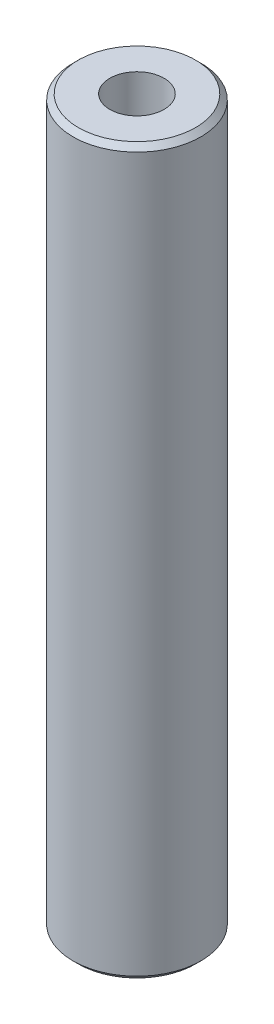
SolidWorks part; units mm, degrees
material "6061-T6 (SS)"
ref_plane "Alzado" through (0, 0, 0) normal (0, 0, 1) x (1, 0, 0)
ref_plane "Planta" through (0, 0, 0) normal (0, 1, 0) x (1, 0, 0)
ref_plane "Vista lateral" through (0, 0, 0) normal (1, 0, 0) x (0, 0, -1)
sketch "Croquis2" plane through (0, 0, 0) normal (0, 1, 0) x (1, 0, 0)
  circle A0 centre (0, 0) radius 4.7625
  dimension "D1" = 9.525
extrude "Saliente-Extruir1" add sketch "Croquis2" along normal mid plane 53.975
chamfer "Chaflán1" distance 0.3969 angle 45 2 edges at (0, -26.9875, 4.7625) (0, 26.9875, 4.7625)
sketch "Croquis3" plane through (0, 0, 0) normal (0, 1, 0) x (1, 0, 0)
  circle A0 centre (0, 0) radius 2.0193
  dimension "D1" = 4.0386
extrude "Tap Hole 1" cut sketch "Croquis3" against normal blind 19.05 from surface starting at face at (0, 26.9875, 4.3656)
extrude "Tap Hole 2" cut sketch "Croquis3<2>" along normal blind 19.05 from surface starting at face at (0, -26.9875, 4.3656)
sketch "Croquis3<2>" plane through (0, 0, 0) normal (0, 1, 0) x (1, 0, 0) same geometry as "Croquis3"
sketch "Croquis4" plane through (0, 0, 0) normal (0, 1, 0) x (1, 0, 0)
  circle A0 centre (0, 0) radius 2.4892
  dimension "D1" = 4.9784
extrude "Clearance Hole" [suppressed] cut sketch "Croquis4" against normal through all both and the other way through all
equation "\"OD\"= 0.375pulgadas"
equation "\"Largo\"= 2.125pulgadas"
equation "\"Tap Hole\"= IIF ( \"OD\" = 0.375pulgadas , 0.1590pulgadas , 0.201pulgadas )"
equation "\"Spacer Hole\"= IIF ( \"OD\" = 0.375pulgadas , 0.196pulgadas , 0.257pulgadas )"
equation "\"D1@Croquis2\"=\"OD\""
equation "\"D1@Saliente-Extruir1\"=\"Largo\""
equation "\"D1@Croquis3\"=\"Tap Hole\""
equation "\"D1@Croquis4\"=\"Spacer Hole\""
